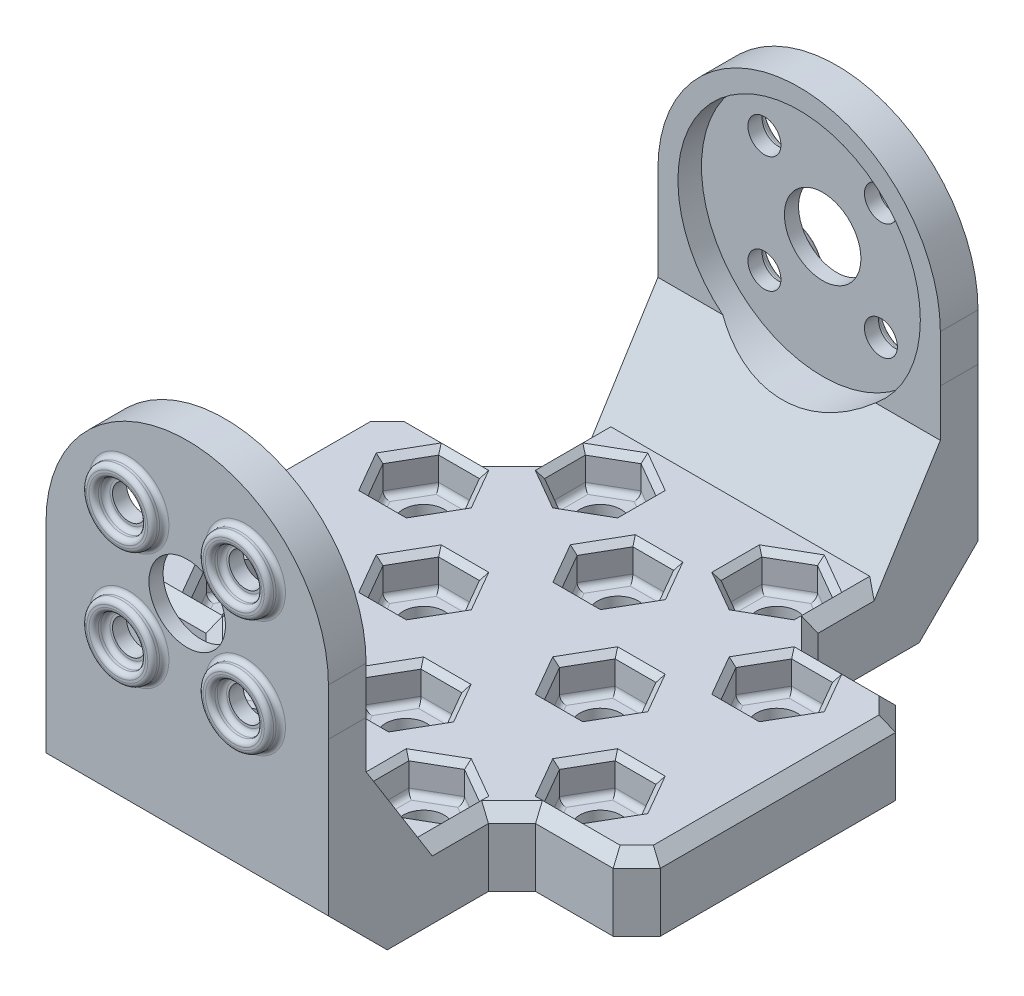
SolidWorks part; units mm, degrees
ref_plane "Спереди" through (0, 0, 0) normal (0, 0, 1) x (1, 0, 0)
ref_plane "Сверху" through (0, 0, 0) normal (0, 1, 0) x (1, 0, 0)
ref_plane "Справа" through (0, 0, 0) normal (1, 0, 0) x (0, 0, -1)
sketch "Эскиз1" plane through (0, 0, 0) normal (0, 0, 1) x (1, 0, 0)
  line L0 (0, 0) -> (0, -58) construction
  line L1 (-4.9497, 4.9497) -> (4.9497, 4.9497) construction
  line L2 (-4.9497, 4.9497) -> (-4.9497, -4.9497) construction
  line L3 (-4.9497, -4.9497) -> (4.9497, -4.9497) construction
  line L4 (4.9497, 4.9497) -> (4.9497, -4.9497) construction
  line L5 (-4.9497, 4.9497) -> (4.9497, -4.9497) construction
  line L6 (-4.9497, -4.9497) -> (4.9497, 4.9497) construction
  line L7 (0, -58) -> (0.0001, -58) construction
  line L8 (10.0001, -28) -> (-9.9999, -28) construction
  line L9 (10.0001, -28) -> (10.0001, -68) construction
  line L10 (-9.9999, -28) -> (-9.9999, -68) construction
  line L11 (-9.9999, -68) -> (10.0001, -68) construction
  line L12 (0.0001, -66.4245) -> (0.0001, -23.0654) construction
  line L13 (-11.9999, -22) -> (12.0001, -22) construction
  line L14 (-11.9999, -22) -> (-11.9999, -42) construction
  line L15 (-11.9999, -42) -> (12.0001, -42) construction
  line L16 (12.0001, -22) -> (12.0001, -42) construction
  line L17 (-11.9999, -22) -> (-11.9999, -16)
  line L18 (-11.9999, -22) -> (12.0001, -22)
  line L19 (12.0001, -22) -> (12.0001, -4)
  line L20 (12.0001, -4) -> (12, 0.0003)
  line L21 (-11.9999, -16) -> (-12, -0.0001)
  circle A0 centre (0, 0) radius 3.25
  circle A1 centre (-4.9497, 4.9497) radius 1.4
  circle A2 centre (4.9497, 4.9497) radius 1.4
  circle A3 centre (4.9497, -4.9497) radius 1.4
  circle A4 centre (-4.9497, -4.9497) radius 1.4
  circle A5 centre (0, 0) radius 10 construction
  circle A6 centre (-7.4999, -30.5) radius 1 construction
  arc A7 (12, 0.0003) -> (-12, -0.0001) centre (0, 0) ccw
  circle A11 centre (0.0001, -58) radius 10 construction
  circle A12 centre (0.0001, -30.25) radius 1 construction
  circle A13 centre (7.0001, -37.25) radius 1 construction
  circle A14 centre (-6.9999, -37.25) radius 1 construction
  point P3 (0, 0)
  point P50 (18.0001, -28)
  dimension "D1" = 6.5
  dimension "D3" = 2.8
  dimension "D6" = 20
  dimension "D9" = 2
  dimension "D15" = 6
  dimension "D16" = 10
  dimension "D17" = 14
  dimension "D21" = 24
  dimension "D22" = 6
  dimension "D20" = 24
  dimension "D2" = 14
  dimension "D4" = 58
  dimension "D5" = 0.0001
  dimension "D7" = 27.5
  dimension "D8" = 7.5
  dimension "D10" = 18
  dimension "D12" = 30
  dimension "D13" = 20
  dimension "D14" = 40
  dimension "D18" = 24
  dimension "D19" = 7
  dimension "D24" = 27.75
  dimension "D25" = 7
  dimension "D26" = 7
extrude "Бобышка-Вытянуть1" add sketch "Эскиз1" along normal blind 3.2
sketch "Эскиз2" plane through (0, 0, 3.2) normal (0, 0, 1) x (1, 0, 0)
  line L1 (12.0001, -22) -> (-11.9999, -22)
  line L2 (12.0001, -22) -> (12.0001, -16)
  line L3 (12.0001, -16) -> (-11.9999, -16)
  line L4 (-11.9999, -22) -> (-11.9999, -16)
extrude "Бобышка-Вытянуть2" add sketch "Эскиз2" along normal blind 48.8
sketch "Эскиз3" plane through (0, 0, 52) normal (0, 0, 1) x (1, 0, 0)
  line L5 (-11.9999, -22) -> (12.0001, -22)
  line L6 (-11.9999, -16) -> (-11.9999, -22)
  line L7 (-12, -0.0001) -> (-11.9999, -16)
  line L8 (12.0001, -4) -> (12, 0.0003)
  line L9 (12.0001, -22) -> (12.0001, -4)
  line L10 (-11.9999, -22) -> (12.0001, -22)
  line L11 (-11.9999, -16) -> (-11.9999, -22)
  line L12 (-12, -0.0001) -> (-11.9999, -16)
  line L13 (12.0001, -4) -> (12, 0.0003)
  line L14 (12.0001, -22) -> (12.0001, -4)
  circle A0 centre (-4.9497, 4.9497) radius 1.4 construction
  arc A1 (12, 0.0003) -> (-12, -0.0001) centre (0, 0) ccw
  arc A2 (12, 0.0003) -> (-12, -0.0001) centre (0, 0) ccw
  circle A3 centre (0, 0) radius 3.25 construction
  circle A4 centre (-4.9497, -4.9497) radius 1.4 construction
  circle A5 centre (4.9497, -4.9497) radius 1.4 construction
  circle A6 centre (4.9497, 4.9497) radius 1.4 construction
  circle A7 centre (-4.9497, 4.9497) radius 1.4
  circle A8 centre (0, 0) radius 3.25
  circle A9 centre (-4.9497, -4.9497) radius 1.4
  circle A10 centre (4.9497, -4.9497) radius 1.4
  circle A11 centre (4.9497, 4.9497) radius 1.4
  dimension "D1" = 0
extrude "Бобышка-Вытянуть3" add sketch "Эскиз3" along normal blind 3.2
sketch "Эскиз4" plane through (0, 0, 3.2) normal (0, 0, 1) x (1, 0, 0)
  circle A0 centre (0, 0) radius 10.3
  dimension "D1" = 20.6
extrude "Вырез-Вытянуть1" cut sketch "Эскиз4" against normal blind 2
sketch "Эскиз5" plane through (0, 0, 52) normal (0, 0, -1) x (-1, 0, 0)
  circle A0 centre (0, 0) radius 10.3 construction
  circle A1 centre (0, 0) radius 10.3
extrude "Вырез-Вытянуть2" cut sketch "Эскиз5" against normal blind 2
chamfer "Фаска1" distance 5 angle 45 2 edges at (0.0001, -22, 0) (0.0001, -22, 55.2)
sketch "Эскиз6" plane through (0, 0, 55.2) normal (0, 0, 1) x (1, 0, 0)
  circle A0 centre (-4.9497, 4.9497) radius 2
  circle A1 centre (-4.9497, 4.9497) radius 3
  circle A2 centre (-4.9497, -4.9497) radius 2
  circle A3 centre (4.9497, -4.9497) radius 2
  circle A4 centre (4.9497, -4.9497) radius 3
  circle A5 centre (-4.9497, -4.9497) radius 3
  circle A6 centre (4.9497, 4.9497) radius 2
  circle A7 centre (4.9497, 4.9497) radius 3
  dimension "D1" = 4
  dimension "D2" = 1
extrude "Бобышка-Вытянуть4" add sketch "Эскиз6" along normal blind 1
sketch "Эскиз7" plane through (0, 0, 0) normal (0, 0, -1) x (-1, 0, 0)
  circle A0 centre (4.9497, -4.9497) radius 3 construction
  circle A1 centre (4.9497, 4.9497) radius 3 construction
  circle A2 centre (-4.9497, 4.9497) radius 3 construction
  circle A3 centre (-4.9497, -4.9497) radius 3 construction
  circle A4 centre (4.9497, -4.9497) radius 3
  circle A5 centre (4.9497, 4.9497) radius 3
  circle A6 centre (-4.9497, 4.9497) radius 3
  circle A7 centre (-4.9497, -4.9497) radius 3
  circle A8 centre (4.9497, 4.9497) radius 2 construction
  circle A9 centre (-4.9497, 4.9497) radius 2 construction
  circle A10 centre (-4.9497, -4.9497) radius 2 construction
  circle A11 centre (4.9497, -4.9497) radius 2 construction
  circle A12 centre (4.9497, 4.9497) radius 2
  circle A13 centre (-4.9497, 4.9497) radius 2
  circle A14 centre (-4.9497, -4.9497) radius 2
  circle A15 centre (4.9497, -4.9497) radius 2
extrude "Бобышка-Вытянуть5" add sketch "Эскиз7" along normal blind 1
fillet "Скругление1" radius 0.4 32 edges at (7.9497, -4.9497, 0) (-1.9497, -4.9497, 0) (1.9497, -4.9497, -1) (2.9497, -4.9497, 0) (2.9497, -4.9497, -1) (-7.9497, -4.9497, -1) (-6.9497, -4.9497, 0) (-6.9497, -4.9497, -1) (-6.9497, 4.9497, 0) (-6.9497, 4.9497, -1) (-1.9497, 4.9497, 0) (-7.9497, 4.9497, -1) (7.9497, 4.9497, 0) (2.9497, 4.9497, 0) (2.9497, 4.9497, -1) (1.9497, 4.9497, -1) (-1.9497, 4.9497, 55.2) (-1.9497, -4.9497, 55.2) (7.9497, -4.9497, 55.2) (7.9497, 4.9497, 55.2) (-1.9497, 4.9497, 56.2) (-2.9497, 4.9497, 55.2) (-2.9497, 4.9497, 56.2) (6.9497, 4.9497, 55.2) (6.9497, 4.9497, 56.2) (7.9497, 4.9497, 56.2) (7.9497, -4.9497, 56.2) (-1.9497, -4.9497, 56.2) (-2.9497, -4.9497, 55.2) (-2.9497, -4.9497, 56.2) (6.9497, -4.9497, 55.2) (6.9497, -4.9497, 56.2)
chamfer "Фаска4" distance 8 distance2 5 1 edges
chamfer "Фаска5" distance 5 distance2 8 1 edges
sketch "Эскиз8" plane through (0, -22, 0) normal (0, -1, 0) x (1, 0, 0)
  line L0 (-11.9999, 50.2) -> (-11.9999, 5) construction
  line L1 (-11.9999, 39.6) -> (-22.6, 39.6)
  line L2 (-11.9999, 39.6) -> (-11.9999, 15.6)
  line L3 (-11.9999, 15.6) -> (-22.6, 15.6)
  line L4 (-22.6, 39.6) -> (-22.6, 15.6)
  line L5 (12.0001, 27.6) -> (-11.9999, 27.6) construction
  line L6 (12.0001, 50.2) -> (12.0001, 5) construction
  line L7 (0, 9.9322) -> (0, 45.3465) construction
  line L8 (12.0001, 39.6) -> (22.6002, 39.6)
  line L9 (12.0001, 39.6) -> (12.0001, 15.6)
  line L10 (12.0001, 15.6) -> (22.6002, 15.6)
  line L11 (22.6002, 39.6) -> (22.6002, 15.6)
  dimension "D1" = 22.6
  dimension "D2" = 24
extrude "Бобышка-Вытянуть6" add sketch "Эскиз8" against normal up to surface (6 mm away) up to face at (0.0001, -16, 32.45)
chamfer "Фаска6" distance 2 angle 45 8 edges at (-11.9999, -19, 15.6) (-11.9999, -19, 39.6) (-22.6, -19, 39.6) (-22.6, -19, 15.6) (22.6002, -19, 15.6) (22.6002, -19, 39.6)
chamfer "Фаска7" distance 1 angle 45 18 edges at (13.0001, -16, 14.6) (21.6002, -16, 16.6) (13.0001, -16, 40.6) (21.6002, -16, 38.6) (22.6002, -16, 27.6) (-11.9999, -16, 44.3) (-11.9999, -16, 10.9) (-12.9999, -16, 14.6) (-17.3, -16, 15.6) (-21.6, -16, 16.6) (-22.6, -16, 27.6) (-21.6, -16, 38.6) (-17.3, -16, 39.6) (-12.9999, -16, 40.6)
sketch "Эскиз9" plane through (0, -16, 0) normal (0, 1, 0) x (1, 0, 0)
  line L0 (0, -45.4303) -> (0, -13.1225) construction
  line L1 (21.6002, -27.6) -> (-21.6, -27.6) construction
  line L2 (21.6002, -37.1858) -> (21.6002, -18.0142) construction
  line L3 (-21.6, -18.0142) -> (-21.6, -37.1858) construction
  circle A0 centre (-15, -35.1) radius 1.75
  circle A1 centre (-15, -20.1) radius 1.75
  circle A2 centre (15, -20.1) radius 1.75
  circle A3 centre (15, -35.1) radius 1.75
  circle A4 centre (7.5001, -42.5999) radius 1.75
  circle A5 centre (-7.4999, -42.5999) radius 1.75
  circle A6 centre (-7.4999, -12.5999) radius 1.75
  circle A7 centre (7.5001, -12.5999) radius 1.75
  circle A8 centre (7.5, -27.6) radius 1.75
  circle A9 centre (-7.5, -27.6) radius 1.75
  circle A10 centre (0, -18.6) radius 1.75
  circle A11 centre (0, -36.6) radius 1.75
  point P28 (0.0001, -27.6)
  point P30 (0.0001, -27.6)
  dimension "D2" = 3.5
  dimension "D1" = 15
  dimension "D3" = 30
  dimension "D5" = 15
  dimension "D6" = 18
  dimension "D4" = 2
extrude "Вырез-Вытянуть3" cut sketch "Эскиз9" against normal up to surface (6 mm away) up to face at (0.0001, -22, 28.03)
sketch "Эскиз11" plane through (0, -16, 0) normal (0, 1, 0) x (1, 0, 0)
  line L1 (-11.5359, -20.1) -> (-13.2679, -17.1)
  line L2 (-13.2679, -17.1) -> (-16.7321, -17.1)
  line L3 (-16.7321, -17.1) -> (-18.4641, -20.1)
  line L4 (-18.4641, -20.1) -> (-16.7321, -23.1)
  line L5 (-16.7321, -23.1) -> (-13.2679, -23.1)
  line L6 (-13.2679, -23.1) -> (-11.5359, -20.1)
  line L7 (-3.4641, -18.6) -> (-1.7321, -21.6)
  line L8 (-1.7321, -21.6) -> (1.7321, -21.6)
  line L9 (1.7321, -21.6) -> (3.4641, -18.6)
  line L10 (3.4641, -18.6) -> (1.7321, -15.6)
  line L11 (1.7321, -15.6) -> (-1.7321, -15.6)
  line L12 (-1.7321, -15.6) -> (-3.4641, -18.6)
  line L13 (-7.4999, -16.064) -> (-4.4999, -14.332)
  line L14 (-4.4999, -14.332) -> (-4.4999, -10.8678)
  line L15 (-4.4999, -10.8678) -> (-7.4999, -9.1358)
  line L16 (-7.4999, -9.1358) -> (-10.4999, -10.8678)
  line L17 (-10.4999, -10.8678) -> (-10.4999, -14.332)
  line L18 (-10.4999, -14.332) -> (-7.4999, -16.064)
  line L19 (4.5001, -10.8678) -> (4.5001, -14.332)
  line L20 (4.5001, -14.332) -> (7.5001, -16.064)
  line L21 (7.5001, -16.064) -> (10.5001, -14.332)
  line L22 (10.5001, -14.332) -> (10.5001, -10.8678)
  line L23 (10.5001, -10.8678) -> (7.5001, -9.1358)
  line L24 (7.5001, -9.1358) -> (4.5001, -10.8678)
  line L25 (18.4641, -20.1) -> (16.7321, -17.1)
  line L26 (16.7321, -17.1) -> (13.2679, -17.1)
  line L27 (13.2679, -17.1) -> (11.5359, -20.1)
  line L28 (11.5359, -20.1) -> (13.2679, -23.1)
  line L29 (13.2679, -23.1) -> (16.7321, -23.1)
  line L30 (16.7321, -23.1) -> (18.4641, -20.1)
  line L31 (18.4641, -35.1) -> (16.7321, -32.1)
  line L32 (16.7321, -32.1) -> (13.2679, -32.1)
  line L33 (13.2679, -32.1) -> (11.5359, -35.1)
  line L34 (11.5359, -35.1) -> (13.2679, -38.1)
  line L35 (13.2679, -38.1) -> (16.7321, -38.1)
  line L36 (16.7321, -38.1) -> (18.4641, -35.1)
  line L37 (10.9641, -27.6) -> (9.2321, -24.6)
  line L38 (9.2321, -24.6) -> (5.7679, -24.6)
  line L39 (5.7679, -24.6) -> (4.0359, -27.6)
  line L40 (4.0359, -27.6) -> (5.7679, -30.6)
  line L41 (5.7679, -30.6) -> (9.2321, -30.6)
  line L42 (9.2321, -30.6) -> (10.9641, -27.6)
  line L43 (-4.0359, -27.6) -> (-5.7679, -24.6)
  line L44 (-5.7679, -24.6) -> (-9.2321, -24.6)
  line L45 (-9.2321, -24.6) -> (-10.9641, -27.6)
  line L46 (-10.9641, -27.6) -> (-9.2321, -30.6)
  line L47 (-9.2321, -30.6) -> (-5.7679, -30.6)
  line L48 (-5.7679, -30.6) -> (-4.0359, -27.6)
  line L49 (-11.5359, -35.1) -> (-13.2679, -32.1)
  line L50 (-13.2679, -32.1) -> (-16.7321, -32.1)
  line L51 (-16.7321, -32.1) -> (-18.4641, -35.1)
  line L52 (-18.4641, -35.1) -> (-16.7321, -38.1)
  line L53 (-16.7321, -38.1) -> (-13.2679, -38.1)
  line L54 (-13.2679, -38.1) -> (-11.5359, -35.1)
  line L55 (3.4641, -36.6) -> (1.7321, -33.6)
  line L56 (1.7321, -33.6) -> (-1.7321, -33.6)
  line L57 (-1.7321, -33.6) -> (-3.4641, -36.6)
  line L58 (-3.4641, -36.6) -> (-1.7321, -39.6)
  line L59 (-1.7321, -39.6) -> (1.7321, -39.6)
  line L60 (1.7321, -39.6) -> (3.4641, -36.6)
  line L61 (10.5001, -40.8678) -> (7.5001, -39.1358)
  line L62 (7.5001, -39.1358) -> (4.5001, -40.8678)
  line L63 (4.5001, -40.8678) -> (4.5001, -44.332)
  line L64 (4.5001, -44.332) -> (7.5001, -46.064)
  line L65 (7.5001, -46.064) -> (10.5001, -44.332)
  line L66 (10.5001, -44.332) -> (10.5001, -40.8678)
  line L67 (-4.4999, -44.332) -> (-4.4999, -40.8678)
  line L68 (-4.4999, -40.8678) -> (-7.4999, -39.1358)
  line L69 (-7.4999, -39.1358) -> (-10.4999, -40.8678)
  line L70 (-10.4999, -40.8678) -> (-10.4999, -44.332)
  line L71 (-10.4999, -44.332) -> (-7.4999, -46.064)
  line L72 (-7.4999, -46.064) -> (-4.4999, -44.332)
  circle A0 centre (-15, -20.1) radius 3 construction
  circle A1 centre (0, -18.6) radius 3 construction
  circle A2 centre (-7.4999, -12.5999) radius 3 construction
  circle A3 centre (7.5001, -12.5999) radius 3 construction
  circle A4 centre (15, -20.1) radius 3 construction
  circle A5 centre (15, -35.1) radius 3 construction
  circle A6 centre (7.5, -27.6) radius 3 construction
  circle A7 centre (-7.5, -27.6) radius 3 construction
  circle A8 centre (-15, -35.1) radius 3 construction
  circle A9 centre (0, -36.6) radius 3 construction
  circle A10 centre (7.5001, -42.5999) radius 3 construction
  circle A11 centre (-7.4999, -42.5999) radius 3 construction
  dimension "D1" = 6
extrude "Вырез-Вытянуть4" cut sketch "Эскиз11" against normal blind 3
chamfer "Фаска8" distance 0.5 angle 45 72 edges at (9.0001, -16, 40.0018) (6.0001, -16, 40.0018) (4.5001, -16, 42.5999) (6.0001, -16, 45.198) (9.0001, -16, 45.198) (10.5001, -16, 42.5999) (-2.5981, -16, 38.1) (0, -16, 39.6) (2.5981, -16, 38.1) (2.5981, -16, 35.1) (0, -16, 33.6) (-2.5981, -16, 35.1) (-7.5, -16, 30.6) (-10.0981, -16, 29.1) (-10.0981, -16, 26.1) (-7.5, -16, 24.6) (-4.9019, -16, 26.1) (-4.9019, -16, 29.1) (-17.5981, -16, 36.6) (-17.5981, -16, 33.6) (-15, -16, 32.1) (-12.4019, -16, 33.6) (-12.4019, -16, 36.6) (-15, -16, 38.1) (-10.4999, -16, 42.5999) (-8.9999, -16, 45.198) (-8.9999, -16, 40.0018) (-5.9999, -16, 45.198) (-4.4999, -16, 42.5999) (-5.9999, -16, 40.0018) (12.4019, -16, 33.6) (12.4019, -16, 36.6) (15, -16, 38.1) (17.5981, -16, 36.6) (17.5981, -16, 33.6) (15, -16, 32.1) (7.5, -16, 24.6) (4.9019, -16, 26.1) (4.9019, -16, 29.1) (7.5, -16, 30.6) (10.0981, -16, 29.1) (10.0981, -16, 26.1) (12.4019, -16, 18.6) (15, -16, 17.1) (17.5981, -16, 18.6) (17.5981, -16, 21.6) (15, -16, 23.1) (12.4019, -16, 21.6) (6.0001, -16, 15.198) (4.5001, -16, 12.5999) (6.0001, -16, 10.0018) (9.0001, -16, 10.0018) (10.5001, -16, 12.5999) (9.0001, -16, 15.198) (-2.5981, -16, 20.1) (0, -16, 21.6) (2.5981, -16, 20.1) (2.5981, -16, 17.1) (0, -16, 15.6) (-2.5981, -16, 17.1) (-5.9999, -16, 15.198) (-4.4999, -16, 12.5999) (-5.9999, -16, 10.0018) (-8.9999, -16, 10.0018) (-10.4999, -16, 12.5999) (-8.9999, -16, 15.198) (-12.4019, -16, 21.6) (-15, -16, 23.1) (-17.5981, -16, 21.6) (-17.5981, -16, 18.6) (-15, -16, 17.1) (-12.4019, -16, 18.6)
fillet "Скругление2" radius 0.5 72 edges at (9.0001, -19, 45.198) (6.0001, -19, 45.198) (4.5001, -19, 42.5999) (6.0001, -19, 40.0018) (9.0001, -19, 40.0018) (10.5001, -19, 42.5999) (0, -19, 39.6) (-2.5981, -19, 38.1) (-2.5981, -19, 35.1) (0, -19, 33.6) (2.5981, -19, 35.1) (2.5981, -19, 38.1) (-8.9999, -19, 45.198) (-10.4999, -19, 42.5999) (-8.9999, -19, 40.0018) (-5.9999, -19, 40.0018) (-4.4999, -19, 42.5999) (-5.9999, -19, 45.198) (-15, -19, 38.1) (-17.5981, -19, 36.6) (-17.5981, -19, 33.6) (-15, -19, 32.1) (-12.4019, -19, 33.6) (-12.4019, -19, 36.6) (-7.5, -19, 30.6) (-10.0981, -19, 29.1) (-10.0981, -19, 26.1) (-7.5, -19, 24.6) (-4.9019, -19, 26.1) (-4.9019, -19, 29.1) (-15, -19, 23.1) (-17.5981, -19, 21.6) (-17.5981, -19, 18.6) (-15, -19, 17.1) (-12.4019, -19, 18.6) (-12.4019, -19, 21.6) (-10.4999, -19, 12.5999) (-8.9999, -19, 10.0018) (-5.9999, -19, 10.0018) (-4.4999, -19, 12.5999) (-5.9999, -19, 15.198) (-8.9999, -19, 15.198) (0, -19, 15.6) (2.5981, -19, 17.1) (2.5981, -19, 20.1) (0, -19, 21.6) (-2.5981, -19, 20.1) (-2.5981, -19, 17.1) (9.0001, -19, 10.0018) (10.5001, -19, 12.5999) (9.0001, -19, 15.198) (6.0001, -19, 15.198) (4.5001, -19, 12.5999) (6.0001, -19, 10.0018) (15, -19, 23.1) (12.4019, -19, 21.6) (12.4019, -19, 18.6) (15, -19, 17.1) (17.5981, -19, 18.6) (17.5981, -19, 21.6) (7.5, -19, 30.6) (4.9019, -19, 29.1) (4.9019, -19, 26.1) (7.5, -19, 24.6) (10.0981, -19, 29.1) (10.0981, -19, 26.1) (12.4019, -19, 36.6) (15, -19, 38.1) (17.5981, -19, 36.6) (17.5981, -19, 33.6) (12.4019, -19, 33.6) (15, -19, 32.1)
